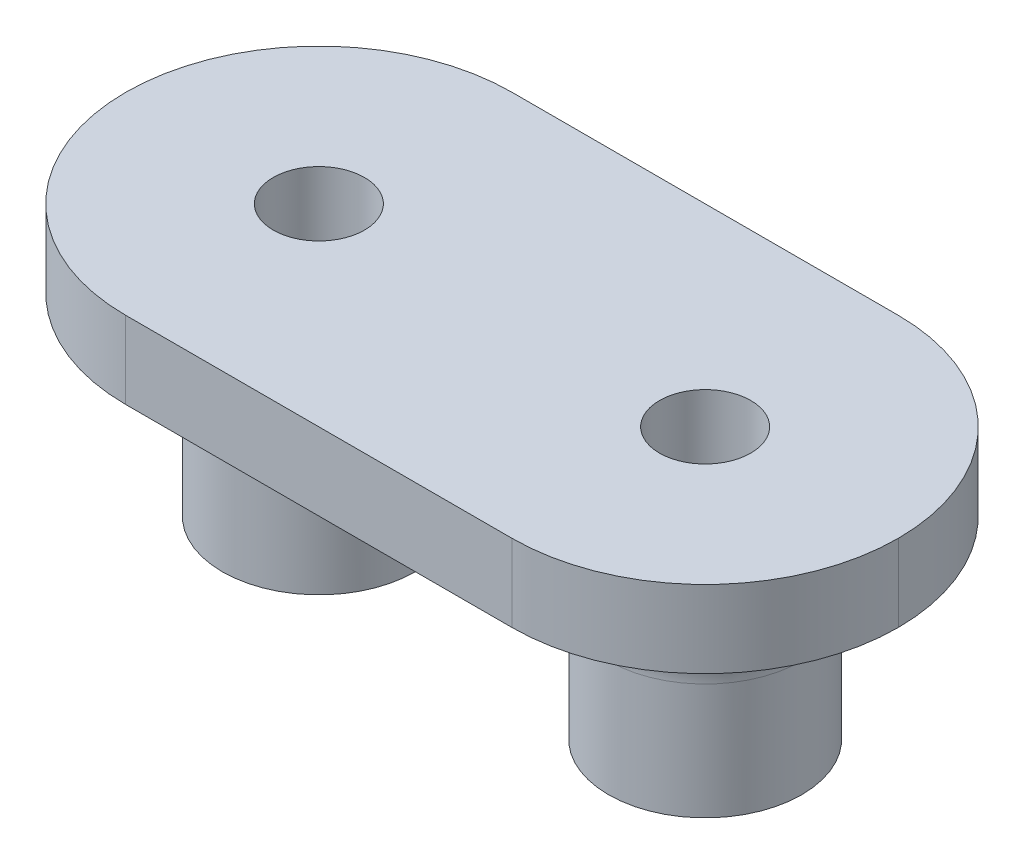
SolidWorks part; units mm, degrees
ref_plane "Front Plane" through (0, 0, 0) normal (0, 0, 1) x (1, 0, 0)
ref_plane "Top Plane" through (0, 0, 0) normal (0, 1, 0) x (1, 0, 0)
ref_plane "Right Plane" through (0, 0, 0) normal (1, 0, 0) x (0, 0, -1)
sketch "Sketch1" plane through (0, 0, 0) normal (0, 1, 0) x (1, 0, 0)
  line L1 (-12.7, 12.7) -> (12.7, 12.7)
  line L2 (-12.7, 12.7) -> (-12.7, -12.7)
  line L3 (-12.7, -12.7) -> (12.7, -12.7)
  line L4 (12.7, 12.7) -> (12.7, -12.7)
  line L5 (-12.7, 12.7) -> (12.7, -12.7) construction
  line L6 (-12.7, -12.7) -> (12.7, 12.7) construction
  line L7 (-6.35, 6.35) -> (6.35, 6.35) construction
  line L8 (-6.35, 6.35) -> (-6.35, -6.35) construction
  line L9 (-6.35, -6.35) -> (6.35, -6.35) construction
  line L10 (6.35, 6.35) -> (6.35, -6.35) construction
  line L11 (-6.35, 6.35) -> (6.35, -6.35) construction
  line L12 (-6.35, -6.35) -> (6.35, 6.35) construction
  circle A0 centre (-6.35, 6.35) radius 1.5
  circle A1 centre (6.35, 6.35) radius 1.5
  circle A2 centre (6.35, -6.35) radius 1.5
  circle A3 centre (-6.35, -6.35) radius 1.5
  point P0 (0, 0)
  point P6 (0, 0)
  dimension "D4" = 3
  dimension "D1" = 25.4
  dimension "D2" = 25.4
  dimension "D3" = 12.7
extrude "Boss-Extrude1" add sketch "Sketch1" along normal blind 2.54
sketch "Sketch3" plane through (0, 0, 0) normal (0, -1, 0) x (1, 0, 0)
  line L0 (-12.7, 0) -> (12.7, 0)
  line L1 (-12.7, -12.7) -> (-12.7, 12.7) construction
  line L2 (12.7, 12.7) -> (12.7, -12.7) construction
  line L3 (12.7, 0) -> (12.7, -12.7)
  line L4 (12.7, -12.7) -> (-12.7, -12.7)
  line L5 (-12.7, -12.7) -> (-12.7, 0)
extrude "Cut-Extrude1" cut sketch "Sketch3" against normal through all
sketch "Sketch4" plane through (0, 0, 0) normal (0, -1, 0) x (1, 0, 0)
  circle A0 centre (-6.35, 6.35) radius 3.175
  circle A1 centre (6.35, 6.35) radius 3.175
  circle A2 centre (6.35, 6.35) radius 1.5 construction
  circle A3 centre (-6.35, 6.35) radius 1.5 construction
  circle A4 centre (6.35, 6.35) radius 1.5
  circle A5 centre (-6.35, 6.35) radius 1.5
  dimension "D1" = 6.35
extrude "Boss-Extrude2" add sketch "Sketch4" along normal blind 6.35
fillet "Fillet1" radius 6.35 4 edges at (12.7, 1.27, 0) (-12.7, 1.27, 0) (-12.7, 1.27, 12.7) (12.7, 1.27, 12.7)
fillet "Fillet2" radius 2.54 2 edges at (6.35, 0, 9.525) (-6.35, 0, 9.525)
